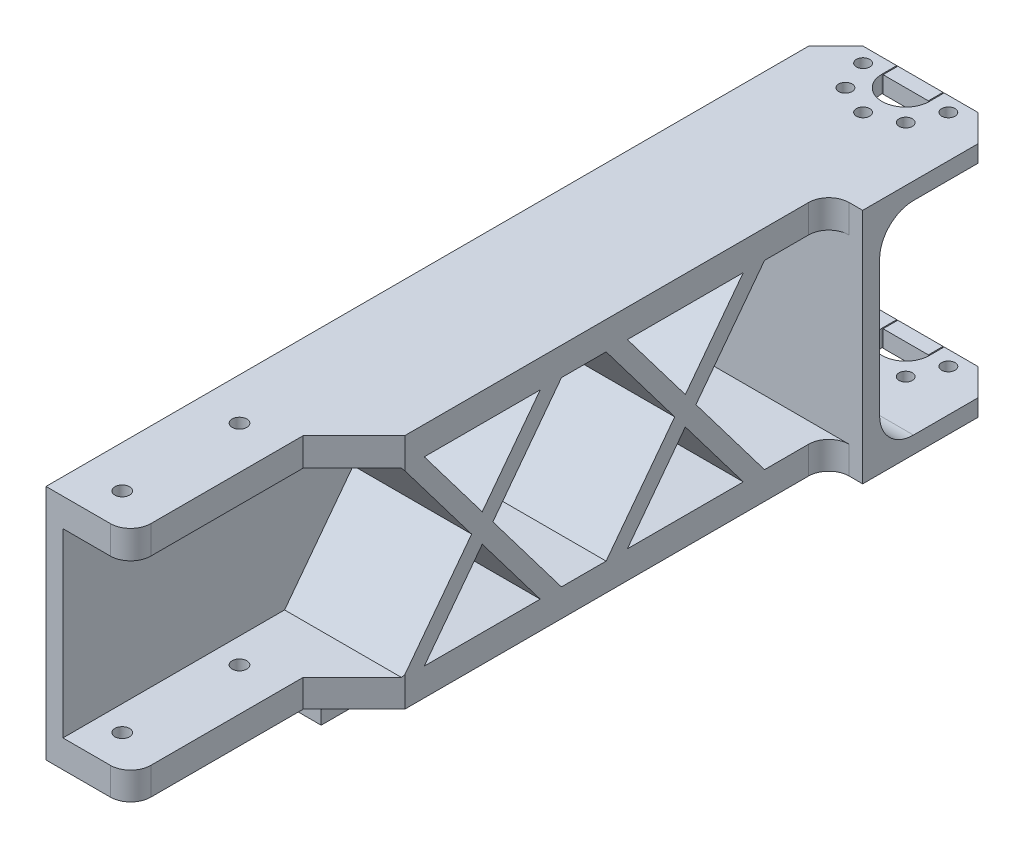
SolidWorks part; units mm, degrees
ref_plane "Front Plane" through (0, 0, 0) normal (0, 0, 1) x (1, 0, 0)
ref_plane "Top Plane" through (0, 0, 0) normal (0, 1, 0) x (1, 0, 0)
ref_plane "Right Plane" through (0, 0, 0) normal (1, 0, 0) x (0, 0, -1)
sketch "Sketch1" plane through (-21, 0, 0) normal (-1, 0, 0) x (0, 0, 1)
  line L0 (72.95, -19) -> (92.05, -19) construction
  line L1 (92.05, 19) -> (72.95, 19) construction
  line L2 (72.95, -19) -> (92.05, -19) construction
  line L3 (92.05, 19) -> (72.95, 19) construction
  line L4 (70.7229, 19.1016) -> (103.275, 19.1016)
  line L5 (103.275, 19.1016) -> (103.275, -19)
  line L6 (103.275, -19) -> (69.575, -19)
  line L7 (69.575, -19) -> (69.575, -22.175)
  line L8 (69.575, -22.175) -> (106.45, -22.175)
  line L9 (106.45, -22.175) -> (106.45, 22.2766)
  line L10 (106.45, 22.2766) -> (70.7229, 22.2766)
  line L11 (70.7229, 22.2766) -> (70.7229, 19.1016)
  line L12 (93.75, -8.4) -> (93.75, 16.6) construction
  line L13 (72.75, -15) -> (72.75, -18.8)
  line L14 (92.25, -18.8) -> (92.25, -17)
  line L15 (92.25, 19.1016) -> (72.75, 19.1016) construction
  line L16 (72.75, -15) -> (72.75, -18.8) construction
  dimension "D1" = 3.175
  dimension "D2" = 3.175
  dimension "D3" = 3.175
  dimension "D4" = 9.525
  dimension "D5" = 3.175
extrude "Boss-Extrude1" add sketch "Sketch1" along normal mid plane 31.75
sketch "Sketch2" plane through (0, -22.175, 0) normal (0, 1, 0) x (1, 0, 0)
  circle A0 centre (-15.3431, -88.1569) radius 1.25
  circle A1 centre (-21, -90.5) radius 1.25
  circle A2 centre (-26.6569, -88.1569) radius 1.25
  circle A3 centre (-29, -82.5) radius 1.25
  circle A4 centre (-26.6569, -76.8431) radius 1.25
  circle A5 centre (-21, -74.5) radius 1.239
  circle A6 centre (-15.3431, -76.8431) radius 1.25
  circle A7 centre (-13, -82.5) radius 1.25
  dimension "D1" = 2.5
extrude "Cut-Extrude1" cut sketch "Sketch2" against normal through all and the other way through all
sketch "Sketch4" plane through (0, 22.2766, 0) normal (0, 1, 0) x (1, 0, 0)
  circle A1 centre (-21, -82.5) radius 4.445
  dimension "D1" = 8.89
extrude "Cut-Extrude2" cut sketch "Sketch4" against normal through all both
sketch "Sketch5" plane through (-36.875, 0, 0) normal (-1, 0, 0) x (0, 0, 1)
  line L1 (106.45, 22.2766) -> (227.925, 22.2766)
  line L2 (106.45, 22.2766) -> (106.45, -22.175)
  line L3 (106.45, -22.175) -> (227.925, -22.175)
  line L4 (227.925, 22.2766) -> (227.925, -22.175)
  line L6 (224.75, 16.6) -> (224.75, -8.4) construction
  dimension "D1" = 3.175
extrude "Boss-Extrude2" add sketch "Sketch5" against normal blind 3.175
sketch "Sketch6" plane through (0, 0, 227.925) normal (0, 0, 1) x (1, 0, 0)
  line L0 (-33.7, -22.175) -> (-36.875, -22.175) construction
  line L1 (-33.7, 22.2766) -> (-11.475, 22.2766)
  line L2 (-33.7, 22.2766) -> (-33.7, 17)
  line L3 (-33.7, 17) -> (-11.475, 17)
  line L4 (-11.475, 22.2766) -> (-11.475, 17)
  line L5 (-33.7, -22.175) -> (-11.475, -22.175)
  line L6 (-33.7, -22.175) -> (-33.7, -17)
  line L7 (-33.7, -17) -> (-11.475, -17)
  line L8 (-11.475, -22.175) -> (-11.475, -17)
  line L9 (-33.7, -22.175) -> (-33.7, 22.2766) construction
  line L10 (-30.0843, -17) -> (-18, -17) construction
  line L11 (12.0843, 17) -> (-30.0843, 17) construction
  dimension "D1" = 22.225
extrude "Boss-Extrude3" add sketch "Sketch6" against normal up to surface (121.475 mm away) up to face at (-19.4125, 0.0508, 106.45)
sketch "Sketch7" plane through (0, 22.2766, 0) normal (0, 1, 0) x (1, 0, 0)
  circle A0 centre (-29, -221.5) radius 1.375
  circle A1 centre (-29, -199.5) radius 1.375
  dimension "D1" = 2.75
extrude "Cut-Extrude3" cut sketch "Sketch7" against normal through all
sketch "Sketch8" plane through (0, -22.175, 0) normal (0, -1, 0) x (1, 0, 0)
  line L0 (-11.475, 227.925) -> (-36.875, 227.925) construction
  line L1 (-21, 227.925) -> (-11.475, 227.925)
  line L2 (-21, 227.925) -> (-21, 196.175)
  line L3 (-21, 196.175) -> (-11.475, 196.175)
  line L4 (-11.475, 227.925) -> (-11.475, 196.175)
  line L5 (-11.475, 106.45) -> (-11.475, 227.925) construction
  dimension "D1" = 31.75
  dimension "D2" = 9.525
extrude "Cut-Extrude4" cut sketch "Sketch8" against normal through all
fillet "Fillet3" radius 3.81 2 edges at (-21, -19.5875, 227.925) (-21, 19.6383, 227.925)
sketch "Sketch9" plane through (-11.475, 0, 0) normal (1, 0, 0) x (0, 0, -1)
  line L1 (-148.2349, -17) -> (-135.3674, 0)
  line L2 (-144.2529, -17) -> (-133.3764, -2.6304)
  line L3 (-133.3764, 2.6304) -> (-144.2529, 17)
  line L4 (-122.4999, -17) -> (-133.3764, -2.6304)
  line L5 (-118.518, -17) -> (-131.3854, 0)
  line L6 (-106.45, 17) -> (-196.175, 17) construction
  line L7 (-106.45, -17) -> (-196.175, -17) construction
  line L8 (-118.518, 17) -> (-122.4999, 17)
  line L9 (-118.518, -17) -> (-122.4999, -17)
  line L10 (-144.2529, -17) -> (-148.2349, -17)
  line L11 (-144.2529, 17) -> (-148.2349, 17)
  line L12 (-135.3674, 0) -> (-148.2349, 17)
  line L15 (-131.3854, 0) -> (-118.518, 17)
  line L16 (-133.3764, 2.6304) -> (-122.4999, 17)
  point P2 (-132.8535, 0.2665)
  point P7 (-133.7336, -0.2418)
  dimension "D1" = 3.175
extrude "Boss-Extrude4" add sketch "Sketch9" against normal up to surface (22.225 mm away) up to face at (-33.7, 0, 167.1875)
pattern_linear "LPattern1" count 2 spacing 38.1 along (0, 0, 1) of "Boss-Extrude4"
fillet "Fillet5" radius 6.35 2 edges at (-21, -19, 103.275) (-21, 19.1016, 103.275)
sketch "Sketch11" plane through (0, 0, 106.45) normal (0, 0, 1) x (1, 0, 0)
  line L1 (-24.175, -22.175) -> (-36.875, -22.175)
  line L2 (-24.175, -22.175) -> (-24.175, -29.638)
  line L3 (-24.175, -29.638) -> (-36.875, -29.638)
  line L4 (-36.875, -22.175) -> (-36.875, -29.638)
  line L6 (-24.175, -22.175) -> (-34.335, -22.175)
  line L7 (-24.175, -22.175) -> (-24.175, -27.098)
  line L8 (-24.175, -27.098) -> (-34.335, -27.098)
  line L9 (-34.335, -22.175) -> (-34.335, -27.098)
  point P4 (-30.525, -29.638)
  dimension "D1" = 2.54
  dimension "D2" = 2.54
  dimension "D3" = 12.7
extrude "Boss-Extrude5" add sketch "Sketch11" along normal blind 82.55 contours L9 L1 L4 L3 L2 L8 region at (-31.9441, -27.3256, 106.45)
fillet "Fillet6" radius 1.27 2 edges at (-34.335, -27.098, 147.725) (-34.335, -22.175, 147.725)
sketch "Sketch12" plane through (0, 0, 189) normal (0, 0, 1) x (1, 0, 0)
  line L0 (-24.175, -27.098) -> (-26.57, -24.7031)
  line L1 (-26.57, -24.7031) -> (-28.965, -27.098)
  line L2 (-24.175, -27.098) -> (-33.065, -27.098) construction
  line L3 (-28.965, -27.098) -> (-24.175, -27.098)
  dimension "D1" = 45
extrude "Boss-Extrude6" add sketch "Sketch12" against normal up to surface (82.55 mm away) up to face at (-32.1783, -25.8869, 106.45)
sketch "Sketch14" plane through (0, -22.175, 0) normal (0, -1, 0) x (1, 0, 0)
  line L0 (-36.875, 69.575) -> (-5.125, 69.575) construction
  line L1 (-5.125, 69.575) -> (-36.875, 69.575)
  line L2 (-5.125, 69.575) -> (-5.125, 79.735)
  line L3 (-5.125, 79.735) -> (-16.555, 79.735)
  line L4 (-36.875, 69.575) -> (-36.875, 79.735)
  line L5 (-21, 79.735) -> (-21, 69.575) construction
  line L6 (-5.125, 74.655) -> (-36.875, 74.655) construction
  line L7 (-36.875, 69.575) -> (-36.875, 106.45) construction
  line L8 (-16.555, 82.5) -> (-16.555, 79.735)
  line L9 (-25.445, 82.5) -> (-25.445, 79.735)
  line L10 (-17.5197, 79.735) -> (-24.4803, 79.735)
  line L11 (-25.445, 79.735) -> (-36.875, 79.735)
  circle A0 centre (-21, 82.5) radius 4.445 construction
  arc A1 (-25.445, 82.5) -> (-24.4803, 79.735) centre (-21, 82.5) ccw
  arc A2 (-17.5197, 79.735) -> (-16.555, 82.5) centre (-21, 82.5) ccw
  point P324 (-21, 74.655)
  dimension "D1" = 10.16
extrude "Cut-Extrude5" cut sketch "Sketch14" against normal through all
sketch "Sketch15" plane through (0, -22.175, 0) normal (0, -1, 0) x (1, 0, 0)
  line L0 (-16.555, 79.735) -> (-16.555, 82.5) construction
  line L1 (-16.755, 82.5) -> (-25.245, 82.5)
  line L2 (-16.755, 82.5) -> (-16.755, 79.735)
  line L3 (-16.755, 79.735) -> (-25.245, 79.735)
  line L4 (-25.245, 82.5) -> (-25.245, 79.735)
  line L5 (-21, 79.735) -> (-21, 82.5) construction
  line L6 (-16.755, 81.1175) -> (-25.245, 81.1175) construction
  line L7 (-25.445, 82.5) -> (-25.445, 79.735) construction
  point P164 (-21, 81.1175)
  dimension "D1" = 0.2
  dimension "D2" = 0.2
extrude "Boss-Extrude7" add sketch "Sketch15" against normal up to surface (3.175 mm away) separate body up to face at (-21, -19, 89.25)
ref_plane "Plane1" through (0, 0.0508, 0) normal (0, -1, 0) x (-1, 0, 0)
sketch "Sketch17" plane through (0, 22.2766, 0) normal (0, 1, 0) x (1, 0, 0)
  line L12 (-16.755, -82.5) -> (-16.755, -79.735)
  line L13 (-16.755, -79.735) -> (-25.245, -79.735)
  line L15 (-25.245, -79.735) -> (-25.245, -82.5)
  line L17 (-25.245, -82.5) -> (-16.755, -82.5)
  line L18 (-16.755, -82.5) -> (-16.755, -79.735)
  line L19 (-16.755, -79.735) -> (-25.245, -79.735)
  line L20 (-25.245, -79.735) -> (-25.245, -82.5)
  line L34 (-25.245, -82.5) -> (-16.755, -82.5)
  dimension "D1" = 0
extrude "Boss-Extrude8" add sketch "Sketch17" against normal up to surface (3.175 mm away) up to face at (-21, 19.1016, 85.2794)
chamfer "Chamfer1" distance 10.16 angle 45 2 edges at (-11.475, 19.6383, 196.175) (-11.475, -19.5875, 196.175)
fillet "Fillet7" radius 3.81 2 edges at (-11.475, 19.6383, 106.45) (-11.475, -19.5875, 106.45)
chamfer "Chamfer2" distance 5.08 angle 45 4 edges at (-36.875, -20.5875, 79.735) (-5.125, -20.5875, 79.735) (-36.875, 20.6891, 79.735) (-5.125, 20.6891, 79.735)
sketch "Sketch18" plane through (-33.7, 0, 0) normal (1, 0, 0) x (0, 0, -1)
  text T0 "NR\r\n2023" font "@Adobe Gothic Std B" height in points 14
extrude "Boss-Extrude9" add sketch "Sketch18" along normal blind 0.762
